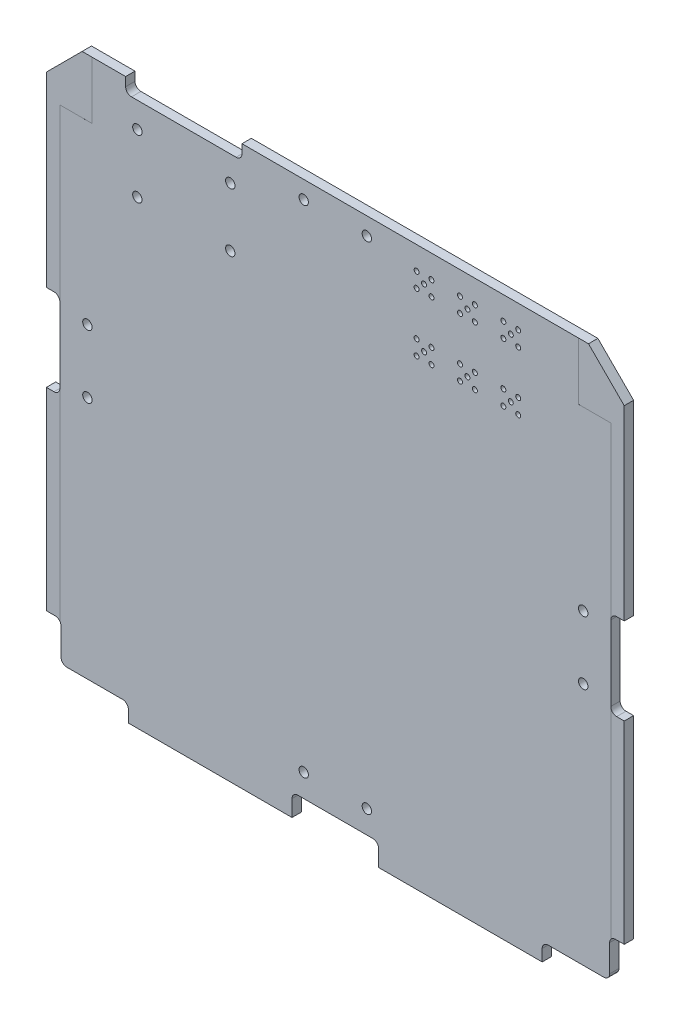
SolidWorks part; units mm, degrees
material "Oshpark board"
ref_plane "Front Plane" through (0, 0, 0) normal (0, 0, 1) x (1, 0, 0)
ref_plane "Top Plane" through (0, 0, 0) normal (0, 1, 0) x (1, 0, 0)
ref_plane "Right Plane" through (0, 0, 0) normal (1, 0, 0) x (0, 0, -1)
ref_plane "Plane4" through (0, 0, -0.0125) normal (0, 0, -1) x (-1, 0, 0)
sketch "Sketch1" plane through (0, 0, -0.0125) normal (0, 0, -1) x (-1, 0, 0)
  line L0 (35.3, -50) -> (35.3, -48)
  line L1 (36.3, -47) -> (45.8, -47)
  line L2 (46.8, -46) -> (46.8, -41.4)
  line L3 (47.8, -40.4) -> (49.3, -40.4)
  line L4 (49.3, -40.4) -> (49.3, 39.2)
  line L5 (49.3, 39.2) -> (43.2, 45.3)
  line L6 (43.2, 45.3) -> (35.5, 45.3)
  line L7 (35.5, 45.3) -> (35.5, 43.8) construction
  line L8 (34.5, 42.8) -> (4.5, 42.8) construction
  line L9 (3.5, 43.8) -> (3.5, 45.3) construction
  line L10 (3.5, 45.3) -> (-43.2, 45.3)
  line L11 (-43.2, 45.3) -> (-49.3, 39.2)
  line L12 (-49.3, 39.2) -> (-49.3, -40.4)
  line L13 (-49.3, -40.4) -> (-47.8, -40.4)
  line L14 (-46.8, -41.4) -> (-46.8, -46)
  line L15 (-45.8, -47) -> (-36.3, -47)
  line L16 (-35.3, -48) -> (-35.3, -50)
  line L17 (-35.3, -50) -> (35.3, -50)
  line L18 (0, -50) -> (0, 45.3) construction
  line L19 (19.5, 42.8) -> (19.5, 25.5258) construction
  line L20 (-13.87, 41.37) -> (-16.41, 38.83) construction
  line L21 (-21.27, 41.37) -> (-23.81, 38.83) construction
  line L22 (-28.67, 41.37) -> (-31.21, 38.83) construction
  line L23 (35.5, 45.3) -> (3.5, 45.3)
  arc A0 (35.3, -48) -> (36.3, -47) centre (36.3, -48) cw
  arc A1 (45.8, -47) -> (46.8, -46) centre (45.8, -46) ccw
  arc A2 (46.8, -41.4) -> (47.8, -40.4) centre (47.8, -41.4) cw
  arc A3 (35.5, 43.8) -> (34.5, 42.8) centre (34.5, 43.8) cw construction
  arc A4 (4.5, 42.8) -> (3.5, 43.8) centre (4.5, 43.8) cw construction
  arc A5 (-47.8, -40.4) -> (-46.8, -41.4) centre (-47.8, -41.4) cw
  arc A6 (-46.8, -46) -> (-45.8, -47) centre (-45.8, -46) ccw
  arc A7 (-36.3, -47) -> (-35.3, -48) centre (-36.3, -48) cw
  circle A8 centre (-21.27, 41.37) radius 0.425
  circle A9 centre (-23.81, 41.37) radius 0.425
  circle A10 centre (-22.54, 40.1) radius 0.425
  circle A11 centre (-13.87, 41.37) radius 0.425
  circle A12 centre (-23.81, 38.83) radius 0.425
  circle A13 centre (-16.41, 41.37) radius 0.425
  circle A14 centre (-15.14, 40.1) radius 0.425
  circle A15 centre (-21.27, 38.83) radius 0.425
  circle A16 centre (-28.67, 41.37) radius 0.425
  circle A17 centre (-31.21, 41.37) radius 0.425
  circle A18 centre (-16.41, 38.83) radius 0.425
  circle A19 centre (-29.94, 40.1) radius 0.425
  circle A20 centre (-31.21, 38.83) radius 0.425
  circle A21 centre (-28.67, 38.83) radius 0.425
  circle A22 centre (33.775, 38.54) radius 0.8 construction
  circle A23 centre (5.225, 38.54) radius 0.8 construction
  circle A24 centre (-13.87, 38.83) radius 0.425
  point P35 (-15.14, 40.1)
  dimension "D7" = 2.5
  dimension "D8" = 1.6
  dimension "D9" = 14.275
  dimension "D10" = 4.26
  dimension "D11" = 1
  dimension "D12" = 1
  dimension "D13" = 1
  dimension "D14" = 1
  dimension "D15" = 1
  dimension "D16" = 1
  dimension "D17" = 1
  dimension "D18" = 1
  dimension "D26" = 0.85
  dimension "D1" = 98.6
  dimension "D2" = 95.3
  dimension "D3" = 14
  dimension "D4" = 9.6
  dimension "D5" = 2.5
  dimension "D6" = 3
  dimension "D19" = 14
  dimension "D20" = 2.5
  dimension "D21" = 6.1
  dimension "D22" = 6.1
  dimension "D23" = 32
  dimension "D24" = 2.54
  dimension "D25" = 2.54
  dimension "D28" = 7.4
  dimension "D29" = 3.93
  dimension "D30" = 35.43
  dimension "D31" = 45
  dimension "D32" = 45
  dimension "D33" = 29.8
  dimension "D34" = 50
  dimension "D27" = 3
extrude "Boss-Extrude1" add sketch "Sketch1" against normal blind 1.6
sketch "thermalContacts_lower" plane through (0, 0, -0.0125) normal (0, 0, -1) x (-1, 0, 0)
  line L3 (47, 35.5) -> (47, -41.5)
  line L4 (41.5, 35.5) -> (41.5, 41.5)
  line L5 (41.5, 35.5) -> (47, 35.5)
  line L9 (-47, 35.5) -> (-47, -41.5)
  line L10 (-41.5, 35.5) -> (-47, 35.5)
  line L11 (-41.5, 35.5) -> (-41.5, 41.5)
  line L14 (-41.5, 41.5) -> (-41.5, 47)
  line L18 (41.5, 41.5) -> (41.5, 47)
  line L19 (-49.3, 39.2) -> (-49.3, -40.4) construction
  line L20 (47, -41.5) -> (59.8273, -41.5)
  line L21 (59.8273, -41.5) -> (59.8273, 47)
  line L22 (-56.1922, 47) -> (-41.5, 47)
  line L23 (41.5, 47) -> (59.8273, 47)
  line L24 (-56.1922, 47) -> (-56.1922, -41.5)
  line L25 (-47, -41.5) -> (-56.1922, -41.5)
  line L26 (49.3, -40.4) -> (49.3, 39.2) construction
  line L27 (-35.3, -50) -> (35.3, -50) construction
  line L28 (43.2, 45.3) -> (-43.2, 45.3) construction
  dimension "D1" = 2.3
  dimension "D2" = 8.5
  dimension "D3" = 1.7
  dimension "D4" = 7.8
  dimension "D5" = 9.8
  dimension "D6" = 8.5
  dimension "D7" = 2.3
  dimension "D8" = 9.8
  dimension "D9" = 7.8
  dimension "D10" = 1.7
sketch "thermalContacts_upper" plane through (0, 0, 1.5875) normal (0, 0, 1) x (1, 0, 0)
  line L3 (-47, 35.5) -> (-47, -41.5)
  line L4 (-41.5, 35.5) -> (-41.5, 41.5)
  line L5 (-41.5, 35.5) -> (-47, 35.5)
  line L9 (47, 35.5) -> (47, -41.5)
  line L10 (41.5, 35.5) -> (47, 35.5)
  line L11 (41.5, 35.5) -> (41.5, 41.5)
  line L14 (41.5, 41.5) -> (41.5, 47)
  line L15 (41.5, 41.5) -> (49.5, 41.5) construction
  line L18 (-41.5, 41.5) -> (-41.5, 47)
  line L19 (-41.5, 41.5) -> (-49.5, 41.5) construction
  line L20 (47, -41.5) -> (59.8273, -41.5)
  line L21 (59.8273, -41.5) -> (59.8273, 47)
  line L22 (59.8273, 47) -> (41.5, 47)
  line L23 (-41.5, 47) -> (-56.1922, 47)
  line L24 (-56.1922, 47) -> (-56.1922, -41.5)
  line L25 (-56.1922, -41.5) -> (-47, -41.5)
pattern_linear "LPattern2" count 2 spacing 10 along (0, -1, 0) of face at (14.295, 41.37, 1.5875) of face at (14.295, 38.83, 1.5875) of face at (15.565, 40.1, 1.5875) of face at (16.835, 38.83, 1.5875) of face at (21.695, 41.37, 1.5875) of face at (21.695, 38.83, 1.5875) of face at (22.965, 40.1, 1.5875) of face at (24.235, 38.83, 1.5875) of face at (24.235, 41.37, 1.5875) of face at (16.835, 41.37, 1.5875) of face at (29.095, 41.37, 1.5875) of face at (29.095, 38.83, 1.5875) of face at (30.365, 40.1, 1.5875) of face at (31.635, 38.83, 1.5875) of face at (31.635, 41.37, 1.5875)
extrude "slotFootprints_REF" cut sketch "thermalContacts_lower" against normal blind 0.0001
extrude "slotFootprints" cut sketch "thermalContacts_upper" against normal blind 0.0001
sketch "Sketch2" plane through (0, 0, 1.5875) normal (0, 0, 1) x (1, 0, 0)
  line L1 (-41.5, 45.3) -> (41.5, 45.3) construction
  line L2 (-49.3, -40.4) -> (-49.3, 39.2) construction
  line L3 (-35.775, 45.3) -> (-35.775, 43.8)
  line L4 (-41.5, 45.3) -> (41.5, 45.3) construction
  line L5 (-34.775, 42.8) -> (-16.925, 42.8)
  line L6 (-15.925, 43.8) -> (-15.925, 45.3)
  line L7 (-15.925, 45.3) -> (-35.775, 45.3)
  arc A1 (-16.925, 42.8) -> (-15.925, 43.8) centre (-16.925, 43.8) ccw
  arc A2 (-35.775, 43.8) -> (-34.775, 42.8) centre (-34.775, 43.8) ccw
  circle A3 centre (-33.775, 38.4723) radius 0.8
  circle A4 centre (-17.925, 38.4723) radius 0.8
  circle A5 centre (-17.925, 28.4723) radius 0.8
  circle A6 centre (-33.775, 28.4723) radius 0.8
  dimension "D2" = 1.6
  dimension "D5" = 1
  dimension "D1" = 15.85
  dimension "D3" = 6.8277
  dimension "D4" = 15.525
  dimension "D6" = 2
  dimension "D7" = 2
  dimension "D8" = 2.5
  dimension "D10" = 10
  dimension "D9" = 2
extrude "20pin_mounts" cut sketch "Sketch2" against normal through all
sketch "Sketch3" plane through (0, 0, -0.0125) normal (0, 0, -1) x (-1, 0, 0)
  line L0 (-49.3, -40.4) -> (-49.3, 39.2) construction
  line L1 (5.39, 42.3) -> (-5.38, 42.3) construction
  line L2 (42.3, -5.39) -> (42.3, 5.38) construction
  line L3 (15.925, 45.3) -> (-41.5, 45.3) construction
  line L4 (5.39, -42.3032) -> (-5.38, -42.3032) construction
  line L5 (-42.3, -5.39) -> (-42.3, 5.38) construction
  line L6 (41.5, 45.3) -> (35.775, 45.3) construction
  line L7 (42.3, -0.005) -> (-42.3, -0.005) construction
  line L8 (0.005, -42.3032) -> (0.005, 42.3) construction
  line L9 (49.3, -40.4) -> (49.3, 39.2) construction
  line L10 (-35.3, -50) -> (35.3, -50) construction
  line L11 (-42.3, -0.005) -> (-49.3, -0.005) construction
  line L12 (42.3, -0.005) -> (49.3, -0.005) construction
  line L13 (49.3, -40.4) -> (49.3, 39.2) construction
  line L14 (-49.3, 7.38) -> (-48, 7.38)
  line L15 (-47, 6.38) -> (-47, -6.39)
  line L16 (-48, -7.39) -> (-49.3, -7.39)
  line L17 (-49.3, -7.39) -> (-49.3, 7.38)
  line L18 (-49.3, -40.4) -> (-49.3, 39.2) construction
  line L19 (-47, 35.5) -> (-47, -40.8) construction
  line L20 (47, -40.8) -> (47, 35.5) construction
  line L21 (48, 7.38) -> (49.3, 7.38)
  line L22 (47, 6.38) -> (47, -6.39)
  line L23 (48, -7.39) -> (49.3, -7.39)
  line L24 (49.3, 7.38) -> (49.3, -7.39)
  line L26 (-6.38, -46.2032) -> (6.39, -46.2032)
  line L27 (-7.38, -47.2032) -> (-7.38, -50)
  line L28 (-7.38, -50) -> (7.39, -50)
  line L29 (7.39, -47.2032) -> (7.39, -50)
  arc A0 (-47, -6.39) -> (-48, -7.39) centre (-48, -6.39) cw
  arc A1 (-48, 7.38) -> (-47, 6.38) centre (-48, 6.38) cw
  circle A2 centre (5.39, 42.3) radius 0.8
  circle A3 centre (-5.38, 42.3) radius 0.8
  arc A4 (47, -6.39) -> (48, -7.39) centre (48, -6.39) ccw
  arc A5 (48, 7.38) -> (47, 6.38) centre (48, 6.38) ccw
  arc A6 (-6.38, -46.2032) -> (-7.38, -47.2032) centre (-6.38, -47.2032) ccw
  circle A7 centre (42.3, 5.38) radius 0.8
  circle A8 centre (42.3, -5.39) radius 0.8
  circle A9 centre (5.39, -42.3032) radius 0.8
  circle A10 centre (-5.38, -42.3032) radius 0.8
  circle A11 centre (-42.3, -5.39) radius 0.8
  circle A12 centre (-42.3, 5.38) radius 0.8
  arc A13 (6.39, -46.2032) -> (7.39, -47.2032) centre (6.39, -47.2032) cw
  point P16 (-47, -0.005)
  point P51 (47, -0.005)
  point P63 (0.005, -46.2032)
  dimension "D1" = 1.6
  dimension "D5" = 39.92
  dimension "D6" = 7
  dimension "D9" = 1
  dimension "D11" = 1
  dimension "D14" = 1
  dimension "D2" = 10.77
  dimension "D3" = 43.92
  dimension "D4" = 3
  dimension "D7" = 7.6968
  dimension "D8" = 2
  dimension "D10" = 2
  dimension "D12" = 3.9
  dimension "D13" = 2
extrude "12pin_mounts" cut sketch "Sketch3" against normal blind 10
